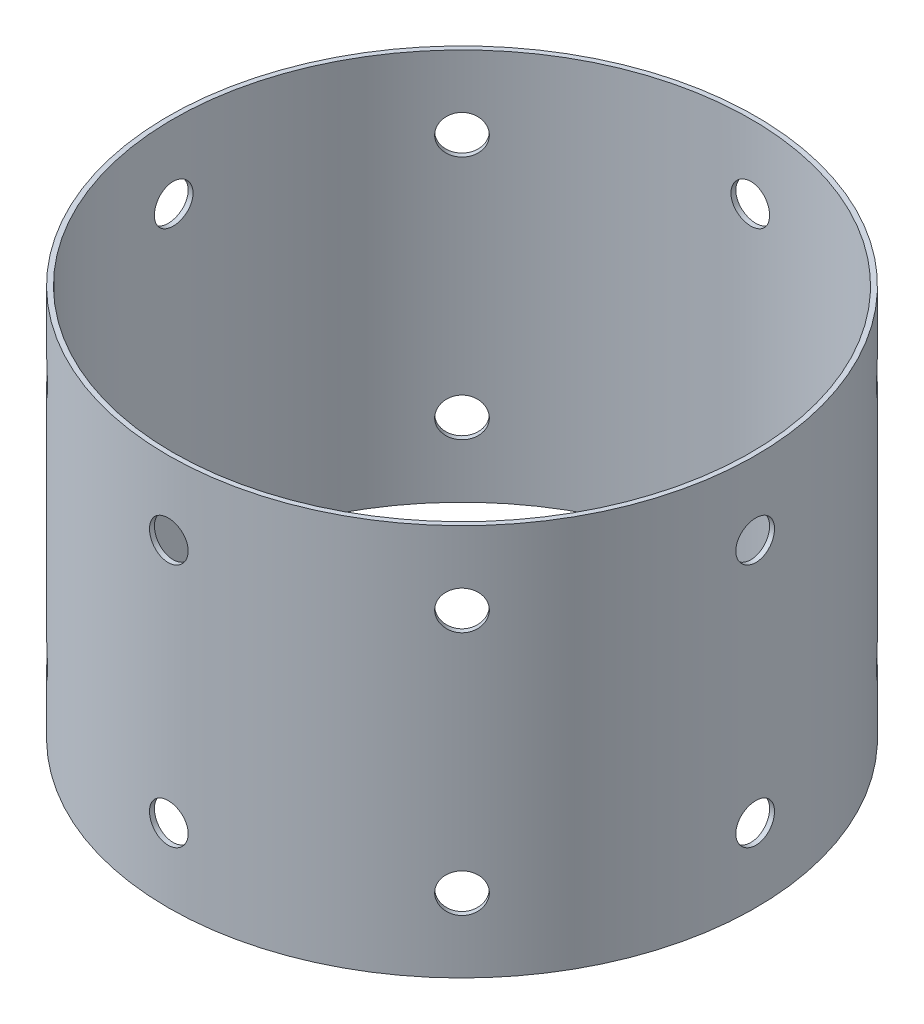
SolidWorks part; units mm, degrees
material "6061-T6 (SS)"
ref_plane "Front Plane" through (0, 0, 0) normal (0, 0, 1) x (1, 0, 0)
ref_plane "Top Plane" through (0, 0, 0) normal (0, 1, 0) x (1, 0, 0)
ref_plane "Right Plane" through (0, 0, 0) normal (1, 0, 0) x (0, 0, -1)
sketch "Sketch2" plane through (0, 0, 0) normal (0, 1, 0) x (1, 0, 0)
  circle A0 centre (0, 0) radius 74.93
  circle A1 centre (0, 0) radius 76.2
  dimension "D1" = 152.4
  dimension "D2" = 1.27
extrude "Boss-Extrude1" add sketch "Sketch2" along normal blind 101.6
sketch "Sketch3" plane through (0, 127, 0) normal (1, 0, 0) x (0, 0, -1)
  circle A0 centre (0, -44.45) radius 4.7625 construction
  circle A1 centre (0, -44.45) radius 4.7625 construction
  circle A2 centre (0, -44.45) radius 5.0165
  dimension "D1" = 0.254
extrude "LOX to Kero, LOX Side Holes" cut sketch "Sketch3" along normal up to surface (76.0347 mm away) up to face at (0, 101.6, 76.2)
pattern_circular "CirPattern1" count 8 over 360 about axis through (0, 101.6, 0) along (0, 1, 0) of "LOX to Kero, LOX Side Holes"
sketch "Sketch4" plane through (0, -25.4, 0) normal (1, 0, 0) x (0, 0, 1)
  circle A0 centre (0, -44.45) radius 4.7625 construction
  circle A1 centre (0, -44.45) radius 4.7625 construction
  circle A2 centre (0, -44.45) radius 5.0165
  dimension "D1" = 0.254
extrude "LOX to Kero, Kero Side Holes" cut sketch "Sketch4" along normal up to surface (76.0347 mm away) up to face at (0, 101.6, 76.2)
pattern_circular "CirPattern2" count 8 over 360 about axis through (0, 0, 0) along (0, 1, 0) of "LOX to Kero, Kero Side Holes"
sketch "Sketch5" [suppressed] plane through (0, -25.4, 0) normal (1, 0, 0) x (0, 0, 1)
  circle A0 centre (0, -44.45) radius 4.7625 construction
  circle A1 centre (0, -44.45) radius 4.7625 construction
  circle A2 centre (0, -44.45) radius 5.0165
  dimension "D1" = 0.254
extrude "N2 to LOX, LOX Side Holes" [suppressed] cut sketch "Sketch5" along normal up to surface (76.0347 mm away) up to face at (0, 101.6, 76.2)
pattern_circular "CirPattern3" [suppressed] count 8 over 360 reverse direction yes of bodies 107
sketch "Sketch7" [suppressed] plane through (0, 0, 0) normal (1, 0, 0) x (0, 0, -1)
  line L0 (-2.3812, 352.7303) -> (2.3812, 352.7303) construction
  line L1 (0, 355.1115) -> (0, 350.349) construction
  line L2 (-2.3813, 629.92) -> (2.3812, 629.92) construction
  line L4 (0, 632.3012) -> (0, 627.5388) construction
  circle A0 centre (0, 629.92) radius 2.3812
  circle A2 centre (0, 352.7303) radius 2.3785
  spline S1 degree 3 poles (-2.3813, 352.7303) (-2.3812, 352.101) (-2.123, 351.4856) (-1.2443, 350.607) (-0.6225, 350.3494) (0.62, 350.3487) (1.2382, 350.6013) (2.1277, 351.4899) (2.381, 352.1078) (2.3815, 353.3511) (2.1241, 353.9729) (1.2468, 354.852) (0.6306, 355.1109) (-0.6258, 355.1122) (-1.2425, 354.8547) (-2.1225, 353.9761) (-2.3813, 353.3596) (-2.3813, 352.7303) (-2.3812, 352.101) (-2.123, 351.4856) knots -0.125 0 0 0 0.125 0.125 0.25 0.25 0.375 0.375 0.5 0.5 0.625 0.625 0.75 0.75 0.875 0.875 1 1 1 1.125 1.125 1.25 only from (-2.3813, 352.7303) to (-2.3813, 352.7303) construction
  spline S2 degree 3 poles (-2.3813, 352.7303) (-2.3812, 352.101) (-2.123, 351.4856) (-1.2443, 350.607) (-0.6225, 350.3494) (0.62, 350.3487) (1.2382, 350.6013) (2.1277, 351.4899) (2.381, 352.1078) (2.3815, 353.3511) (2.1241, 353.9729) (1.2468, 354.852) (0.6306, 355.1109) (-0.6258, 355.1122) (-1.2425, 354.8547) (-2.1225, 353.9761) (-2.3813, 353.3596) (-2.3813, 352.7303) (-2.3812, 352.101) (-2.123, 351.4856) knots -0.125 0 0 0 0.125 0.125 0.25 0.25 0.375 0.375 0.5 0.5 0.625 0.625 0.75 0.75 0.875 0.875 1 1 1 1.125 1.125 1.25 only from (-2.3813, 352.7303) to (-2.3813, 352.7303) construction
  spline S3 degree 3 poles (-2.3813, 629.92) (-2.3812, 629.2907) (-2.123, 628.6754) (-1.2443, 627.7967) (-0.6225, 627.5391) (0.62, 627.5384) (1.2382, 627.791) (2.1277, 628.6797) (2.381, 629.2975) (2.3815, 630.5408) (2.1241, 631.1626) (1.2468, 632.0417) (0.6306, 632.3006) (-0.6258, 632.3019) (-1.2425, 632.0444) (-2.1225, 631.1658) (-2.3813, 630.5493) (-2.3813, 629.92) (-2.3812, 629.2907) (-2.123, 628.6754) knots -0.125 0 0 0 0.125 0.125 0.25 0.25 0.375 0.375 0.5 0.5 0.625 0.625 0.75 0.75 0.875 0.875 1 1 1 1.125 1.125 1.25 only from (-2.3813, 629.92) to (-2.3813, 629.92) construction
  point P8 (0, 352.7303)
  point P17 (0, 629.92)
extrude "Cut-Extrude2" [suppressed] cut sketch "Sketch7" against normal through all both and the other way through all
